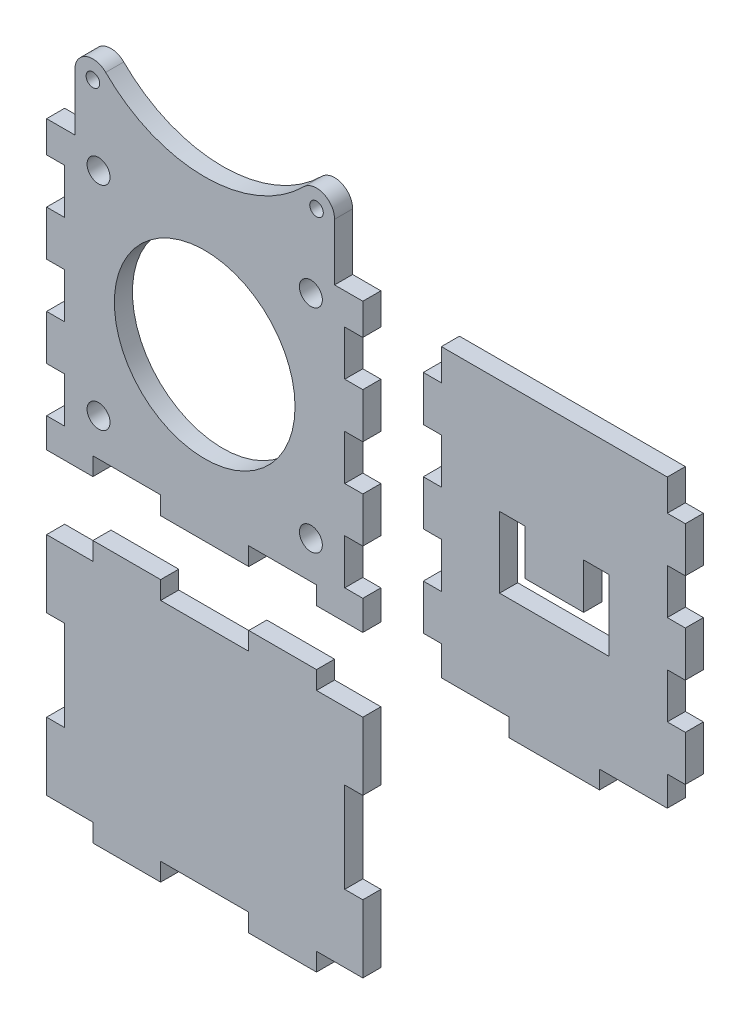
SolidWorks part; units mm, degrees
ref_plane "Front Plane" through (0, 0, 0) normal (0, 0, 1) x (1, 0, 0)
ref_plane "Top Plane" through (0, 0, 0) normal (0, 1, 0) x (1, 0, 0)
ref_plane "Right Plane" through (0, 0, 0) normal (1, 0, 0) x (0, 0, -1)
sketch "Sketch1" plane through (0, 0, 0) normal (0, 0, 1) x (1, 0, 0)
  line L0 (-24.7487, -24.7487) -> (0, 0) construction
  line L1 (0, 0) -> (24.7487, -24.7487) construction
  line L2 (0, -37.3307) -> (0, -35) construction
  line L3 (-35, -100.8307) -> (35, -100.8307)
  line L4 (-28.7487, -24.7487) -> (-28.7487, -37.3307)
  line L5 (-35, -64.2788) -> (-31, -64.2788)
  line L6 (28.7487, -24.7487) -> (28.7487, -37.3307)
  line L7 (-35, -100.8307) -> (-35, -37.3307)
  line L8 (-35, -37.3307) -> (-28.7487, -37.3307)
  line L9 (35, -100.8307) -> (35, -37.3307)
  line L10 (-23.5, -41.5497) -> (23.5, -41.5497) construction
  line L11 (-35, -44.2788) -> (-31, -44.2788)
  line L12 (-35, -44.2788) -> (-35, -54.2788)
  line L13 (-35, -54.2788) -> (-31, -54.2788)
  line L14 (-31, -44.2788) -> (-31, -54.2788)
  line L15 (23.5, -41.5497) -> (23.5, -88.5497) construction
  line L16 (23.5, -88.5497) -> (-23.5, -88.5497) construction
  line L17 (-23.5, -88.5497) -> (-23.5, -41.5497) construction
  line L18 (0, -37.3307) -> (0, -41.5497) construction
  line L19 (28.7487, -37.3307) -> (35, -37.3307)
  line L20 (-35, -64.2788) -> (-35, -74.2788)
  line L21 (-31, -64.2788) -> (-31, -74.2788)
  line L22 (-35, -74.2788) -> (-31, -74.2788)
  line L23 (-35, -84.2788) -> (-31, -84.2788)
  line L24 (-35, -84.2788) -> (-35, -94.2788)
  line L25 (-31, -84.2788) -> (-31, -94.2788)
  line L26 (-35, -94.2788) -> (-31, -94.2788)
  line L27 (35, -64.2788) -> (31, -64.2788)
  line L28 (35, -44.2788) -> (31, -44.2788)
  line L29 (35, -44.2788) -> (35, -54.2788)
  line L30 (35, -54.2788) -> (31, -54.2788)
  line L31 (31, -44.2788) -> (31, -54.2788)
  line L32 (31, -64.2788) -> (31, -74.2788)
  line L33 (35, -74.2788) -> (31, -74.2788)
  line L34 (35, -84.2788) -> (31, -84.2788)
  line L35 (31, -84.2788) -> (31, -94.2788)
  line L36 (35, -94.2788) -> (31, -94.2788)
  line L37 (-9.7487, -96.8307) -> (9.7487, -96.8307) construction
  line L38 (-24.7487, -100.8307) -> (-9.7487, -100.8307)
  line L39 (-24.7487, -100.8307) -> (-24.7487, -96.8307)
  line L40 (-24.7487, -96.8307) -> (-9.7487, -96.8307)
  line L41 (-9.7487, -100.8307) -> (-9.7487, -96.8307)
  line L42 (9.7487, -100.8307) -> (24.7487, -100.8307)
  line L43 (9.7487, -100.8307) -> (9.7487, -96.8307)
  line L44 (9.7487, -96.8307) -> (24.7487, -96.8307)
  line L45 (24.7487, -100.8307) -> (24.7487, -96.8307)
  line L46 (-24.7487, -96.8307) -> (-35, -96.8307) construction
  line L47 (0, -88.5497) -> (0, -96.8307) construction
  line L48 (24.7487, -96.8307) -> (35, -96.8307) construction
  line L49 (87.3929, -100.8307) -> (102.3929, -100.8307)
  line L50 (52.3929, -37.3307) -> (102.3929, -37.3307)
  line L51 (52.3929, -37.3307) -> (52.3929, -44.2788)
  line L52 (52.3929, -100.8307) -> (67.3929, -100.8307)
  line L53 (102.3929, -37.3307) -> (102.3929, -44.2788)
  line L54 (52.3929, -44.2788) -> (48.3929, -44.2788)
  line L55 (102.3929, -54.2788) -> (102.3929, -64.2788)
  line L56 (52.3929, -54.2788) -> (48.3929, -54.2788)
  line L57 (48.3929, -44.2788) -> (48.3929, -54.2788)
  line L58 (52.3929, -64.2788) -> (48.3929, -64.2788)
  line L59 (52.3929, -94.2788) -> (52.3929, -100.8307)
  line L60 (52.3929, -74.2788) -> (48.3929, -74.2788)
  line L61 (48.3929, -64.2788) -> (48.3929, -74.2788)
  line L62 (52.3929, -84.2788) -> (48.3929, -84.2788)
  line L63 (102.3929, -94.2788) -> (102.3929, -100.8307)
  line L64 (52.3929, -94.2788) -> (48.3929, -94.2788)
  line L65 (48.3929, -84.2788) -> (48.3929, -94.2788)
  line L66 (106.3929, -44.2788) -> (102.3929, -44.2788)
  line L67 (106.3929, -44.2788) -> (106.3929, -54.2788)
  line L68 (106.3929, -54.2788) -> (102.3929, -54.2788)
  line L69 (102.3929, -74.2788) -> (102.3929, -84.2788)
  line L70 (102.3929, -64.2788) -> (106.3929, -64.2788)
  line L71 (52.3929, -74.2788) -> (52.3929, -84.2788)
  line L72 (102.3929, -74.2788) -> (106.3929, -74.2788)
  line L73 (106.3929, -64.2788) -> (106.3929, -74.2788)
  line L74 (102.3929, -84.2788) -> (106.3929, -84.2788)
  line L75 (31, -132.0703) -> (31, -117.0703) construction
  line L76 (102.3929, -94.2788) -> (106.3929, -94.2788)
  line L77 (106.3929, -84.2788) -> (106.3929, -94.2788)
  line L78 (52.3929, -54.2788) -> (52.3929, -64.2788)
  line L79 (67.3929, -100.8307) -> (67.3929, -104.8307)
  line L80 (67.3929, -104.8307) -> (87.3929, -104.8307)
  line L81 (87.3929, -100.8307) -> (87.3929, -104.8307)
  line L82 (-35, -117.0703) -> (35, -117.0703)
  line L83 (-35, -117.0703) -> (-35, -167.0703)
  line L84 (-35, -167.0703) -> (35, -167.0703)
  line L85 (35, -117.0703) -> (35, -167.0703)
  line L86 (-24.7487, -117.0703) -> (-9.7487, -117.0703)
  line L87 (-24.7487, -117.0703) -> (-24.7487, -113.0703)
  line L88 (-24.7487, -113.0703) -> (-9.7487, -113.0703)
  line L89 (-9.7487, -117.0703) -> (-9.7487, -113.0703)
  line L90 (9.7487, -117.0703) -> (24.7487, -117.0703)
  line L91 (9.7487, -117.0703) -> (9.7487, -113.0703)
  line L92 (9.7487, -113.0703) -> (24.7487, -113.0703)
  line L93 (24.7487, -117.0703) -> (24.7487, -113.0703)
  line L94 (-24.7487, -167.0703) -> (-9.7487, -167.0703)
  line L95 (-24.7487, -167.0703) -> (-24.7487, -171.0703)
  line L96 (-24.7487, -171.0703) -> (-9.7487, -171.0703)
  line L97 (-9.7487, -167.0703) -> (-9.7487, -171.0703)
  line L98 (9.7487, -167.0703) -> (24.7487, -167.0703)
  line L99 (9.7487, -167.0703) -> (9.7487, -171.0703)
  line L100 (9.7487, -171.0703) -> (24.7487, -171.0703)
  line L101 (24.7487, -167.0703) -> (24.7487, -171.0703)
  line L102 (35, -132.0703) -> (31, -132.0703)
  line L103 (35, -132.0703) -> (35, -152.0703)
  line L104 (35, -152.0703) -> (31, -152.0703)
  line L105 (31, -132.0703) -> (31, -152.0703)
  line L106 (-35, -132.0703) -> (-31, -132.0703)
  line L107 (-35, -132.0703) -> (-35, -152.0703)
  line L108 (-35, -152.0703) -> (-31, -152.0703)
  line L109 (-31, -132.0703) -> (-31, -152.0703)
  line L110 (31, -152.0703) -> (31, -167.0703) construction
  line L111 (65.2727, -78.1598) -> (52.3929, -78.1598) construction
  line L112 (65.2727, -62.4817) -> (70.8931, -62.4817)
  line L113 (65.2727, -62.4817) -> (65.2727, -78.1598)
  line L114 (65.2727, -78.1598) -> (70.8931, -78.1598)
  line L115 (70.8931, -62.4817) -> (70.8931, -78.1598)
  line L116 (83.8928, -62.4817) -> (89.5132, -62.4817)
  line L117 (83.8928, -62.4817) -> (83.8928, -78.1598)
  line L118 (83.8928, -78.1598) -> (89.5132, -78.1598)
  line L119 (89.5132, -62.4817) -> (89.5132, -78.1598)
  line L120 (70.8931, -78.1598) -> (83.8928, -78.1598)
  line L121 (70.8931, -78.1598) -> (70.8931, -72.5394)
  line L122 (70.8931, -72.5394) -> (83.8928, -72.5394)
  line L123 (83.8928, -78.1598) -> (83.8928, -72.5394)
  line L124 (89.5132, -78.1598) -> (102.3929, -78.1598) construction
  line L125 (77.3929, -72.5394) -> (77.3929, -78.1598) construction
  line L126 (-23.5, -41.5497) -> (23.5, -88.5497) construction
  circle A0 centre (0, 0) radius 30 construction
  circle A1 centre (-24.7487, -24.7487) radius 5 construction
  circle A2 centre (24.7487, -24.7487) radius 5 construction
  circle A3 centre (-24.7487, -24.7487) radius 1.5
  circle A4 centre (24.7487, -24.7487) radius 1.5
  arc A5 (-24.7487, -24.7487) -> (24.7487, -24.7487) centre (0, 0) ccw construction
  circle A6 centre (23.5, -41.5497) radius 2.54
  arc A7 (-21.9203, -21.9203) -> (21.9203, -21.9203) centre (0, 0) ccw
  arc A8 (-21.9203, -21.9203) -> (-28.7487, -24.7487) centre (-24.7487, -24.7487) ccw
  arc A9 (28.7487, -24.7487) -> (21.9203, -21.9203) centre (24.7487, -24.7487) ccw
  circle A10 centre (23.5, -88.5497) radius 2.54
  circle A11 centre (-23.5, -88.5497) radius 2.54
  circle A12 centre (-23.5, -41.5497) radius 2.54
  circle A13 centre (0, -65.0497) radius 20
  point P10 (0, -35)
  dimension "D1" = 3
  dimension "D2" = 3
extrude "Boss-Extrude1" add sketch "Sketch1" along normal blind 4 contours L6 A10 A8 A9 L4 L8 L7 L11 L14 L13 L5 L21 L22 L23 L25 L26 L3 L39 L40 L41 L43 L44 L45 L19 L36 L35 L34 L33 L32 L27 L30 L31 L28 L29 L126 A12 A11 A4 | A0 L89 L88 L87 L83 L84 L106 L109 L108 L103 L86 L95 L96 L97 L94 L99 L100 L101 L98 L107 L104 L105 L102 L85 L90 L93 L92 L91 | L81 L49 L64 L77 L78 L74 L71 L76 L73 L70 L56 L69 L67 L66 L55 L50 L53 L54 L59 L57 L82 L58 L63 L61 L72 L62 L68 L65 L60 L52 L79 L80 L115 L122 L117 L116 L119 L118 L120 L114 L113 L112 | L82 L93 L92 L91 | L101 L84 L99 L100 | L97 L84 L95 L96 | L88 L89 L86 L87 region at (-33.9364, -97.5548, 0) region at (77.3929, -69.7188, 0) region at (0, -142.0703, 0) region at (17.2487, -115.0703, 0) region at (-17.2487, -169.0703, 0) region at (17.2487, -169.0703, 0)
